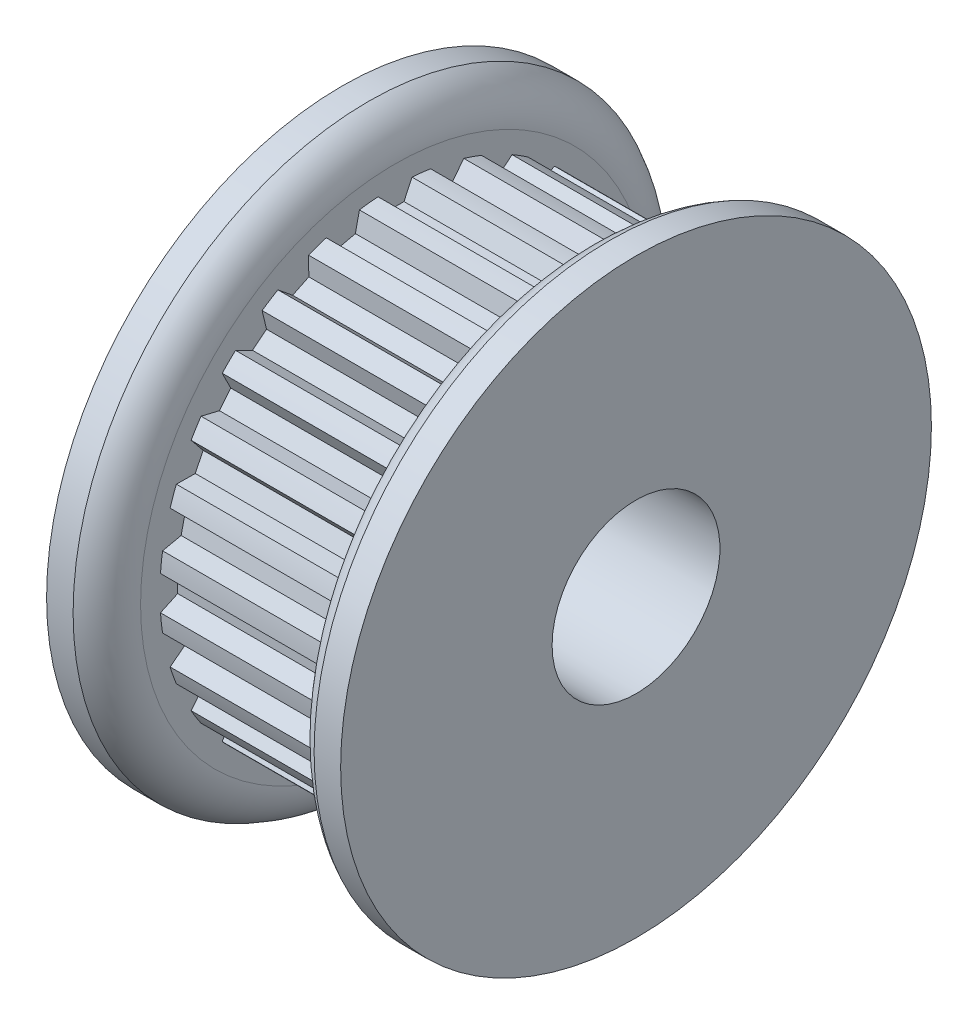
SolidWorks part; units mm, degrees
ref_plane "Front Plane" through (0, 0, 0) normal (0, 0, 1) x (1, 0, 0)
ref_plane "Top Plane" through (0, 0, 0) normal (0, 1, 0) x (1, 0, 0)
ref_plane "Right Plane" through (0, 0, 0) normal (1, 0, 0) x (0, 0, -1)
sketch "Sketch2" plane through (0, 0, 0) normal (1, 0, 0) x (0, 0, -1)
  line L3 (0, 0) -> (0, 8.2296) construction
  line L6 (0, -8.7376) -> (0, -9.0551) construction
  line L7 (-0.5715, 8.7189) -> (-0.3401, 8.2226)
  line L8 (0.5715, 8.7189) -> (0.3401, 8.2226)
  line L9 (-0.5715, 8.7189) -> (-0.6434, 8.8731)
  line L10 (0.5715, 8.7189) -> (0.6434, 8.8731)
  line L12 (-0.3401, 8.2226) -> (0.3401, 8.2226)
  line L14 (0, 8.7376) -> (0, 9.0551) construction
  line L15 (0, 0) -> (0, -1.143) construction
  circle A0 centre (0, 0) radius 9.0551 construction
  circle A1 centre (0, 0) radius 8.2296 construction
  circle A2 centre (0, 0) radius 8.7376 construction
  arc A7 (0.6434, 8.8731) -> (-0.6434, 8.8731) centre (0, 0) ccw
  point P5 (0, 8.8963)
  dimension "D3" = 0.3175
  dimension "D1" = 50
sketch "Sketch1" plane through (0, 0, 0) normal (0, 0, 1) x (1, 0, 0)
  line L0 (-8.7376, 0) -> (8.7376, 0) construction
  line L1 (-8.7376, 3.175) -> (8.7376, 3.175)
  line L2 (-8.7376, 3.175) -> (-8.7376, 8.7376)
  line L3 (-2.3876, 11.176) -> (-1.3843, 11.176)
  line L4 (-0.381, 9.0551) -> (-0.381, 9.6266)
  line L5 (-0.381, 10.1981) -> (-0.381, 9.0551) construction
  line L6 (-0.381, 9.0551) -> (6.731, 9.0551)
  line L7 (6.731, 9.0551) -> (6.731, 9.6266)
  line L8 (6.731, 9.0551) -> (8.7376, 9.0551) construction
  line L9 (7.7343, 11.176) -> (8.7376, 11.176)
  line L10 (8.7376, 11.176) -> (8.7376, 3.175)
  line L11 (7.7343, 9.0551) -> (7.7343, 11.176) construction
  line L12 (-5.5626, 8.7376) -> (-5.5626, 3.175) construction
  line L13 (-2.3876, 11.176) -> (-2.3876, 8.7376)
  line L14 (-2.3876, 8.7376) -> (-8.7376, 8.7376)
  arc A0 (6.731, 9.6266) -> (7.7343, 11.176) centre (8.429, 9.6266) cw
  arc A1 (-0.381, 9.6266) -> (-1.3843, 11.176) centre (-2.079, 9.6266) ccw
  dimension "Bore Size" = 6.35
  dimension "Overall Width" = 17.4752
  dimension "Inside Width" = 7.112
  dimension "OD" = 22.352
  dimension "D2" = 18.1102
  dimension "D3" = 1.143
  dimension "D4" = 0.5715
  dimension "Outside Width" = 11.1252
revolve "Revolve1" add sketch "Sketch1" angle 360 mid plane about L0
sketch "Sketch4" plane through (-0.381, 0, 0) normal (1, 0, 0) x (0, 0, -1)
  circle A0 centre (0, 0) radius 8.8963
  circle A2 centre (0, 0) radius 9.0551
  circle A3 centre (0, 0) radius 9.0551 construction
extrude "Cut-Extrude2" cut sketch "Sketch4" along normal up to surface (7.112 mm away) up to face at (6.731, 0, 9.0551)
sketch "Sketch3" plane through (-0.381, 0, 0) normal (1, 0, 0) x (0, 0, -1)
  line L2 (-0.5715, 8.7189) -> (-0.3401, 8.2226) construction
  line L3 (-0.3401, 8.2226) -> (0.3401, 8.2226) construction
  line L4 (0.5715, 8.7189) -> (0.3401, 8.2226) construction
  line L5 (-0.6434, 8.8731) -> (-0.3401, 8.2226)
  line L6 (-0.3401, 8.2226) -> (0.3401, 8.2226)
  line L7 (0.6434, 8.8731) -> (0.3401, 8.2226)
  arc A1 (0.6434, 8.8731) -> (-0.6434, 8.8731) centre (0, 0) ccw construction
  arc A2 (0.6434, 8.8731) -> (-0.6434, 8.8731) centre (0, 0) ccw
extrude "Cut-Extrude1" cut sketch "Sketch3" along normal up to surface (7.112 mm away) up to face at (6.731, 0, 9.6266)
pattern_circular "CirPattern1" count 28 over 360 of "Cut-Extrude1"
sketch "Sketch5" plane through (0, 0, 0) normal (0, 0, 1) x (1, 0, 0)
  line L1 (6.731, 9.6266) -> (6.731, -9.6266) construction
  point P0 (6.731, 0)
sketch "Sketch6" plane through (-8.7376, 0, 0) normal (-1, 0, 0) x (0, 0, 1)
  circle A0 centre (0, 0) radius 8.7376
  circle A1 centre (0, 0) radius 8.7376 construction
extrude "Cut-Extrude3" cut sketch "Sketch6" against normal up to surface (6.35 mm away) up to face at (-2.3876, 0, 8.7376)
equation "\"D3@Sketch2\" = (\"hs@Sketch2\"-\"ht@Sketch2\")/2"
equation "\"D2@Sketch1\" = \"PD@Sketch2\""
equation "\"D3@Sketch1\" = \"hs@Sketch2\""
equation "\"D4@Sketch1\" = \"D3@Sketch1\"/2"
